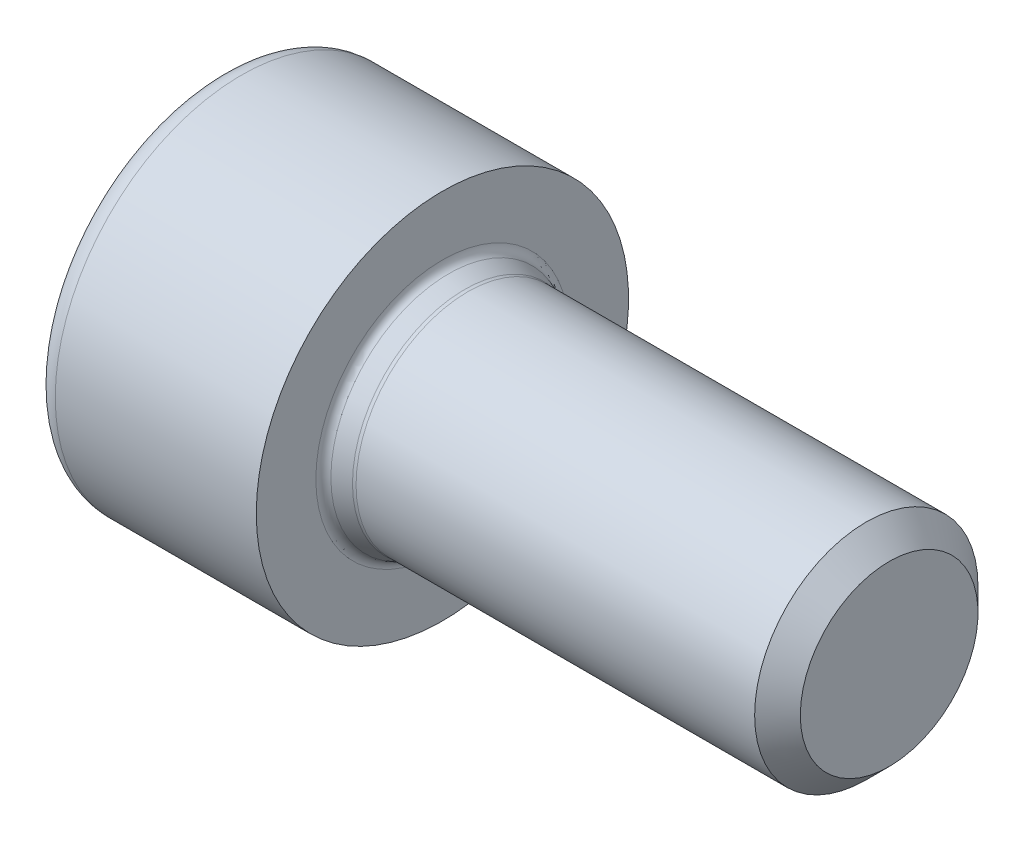
SolidWorks part; units mm, degrees
note: '?' marks a value the reader was unsure of.
ref_plane "前视基准面" through (0, 0, 0) normal (0, 0, 1) x (1, 0, 0)
ref_plane "上视基准面" through (0, 0, 0) normal (0, 1, 0) x (1, 0, 0)
ref_plane "右视基准面" through (0, 0, 0) normal (1, 0, 0) x (0, 0, -1)
sketch "草图1" plane through (0, 0, 0) normal (0, 0, 1) x (1, 0, 0)
  line L0 (-0.8566, 0) -> (-2.3, 2.5)
  line L1 (-2.3, 2.5) -> (-6, 2.5)
  line L2 (-6, 2.5) -> (-6, 4.4)
  line L3 (-5.4, 5) -> (0, 5)
  line L4 (0, 5) -> (0, 3.4)
  line L5 (0.1677, 3.1639) -> (0.5977, 3.0139)
  line L6 (0.68, 3) -> (11.3865, 3)
  line L7 (11.3865, 3) -> (12, 2.3865)
  line L8 (12, 2.3865) -> (12, 0)
  line L9 (12, 0) -> (-0.8566, 0)
  line L10 (12, 0) -> (-0.8566, 0) construction
  arc A0 (-6, 4.4) -> (-5.4, 5) centre (-5.4, 4.4) cw
  arc A1 (0, 3.4) -> (0.1677, 3.1639) centre (0.25, 3.4) ccw
  arc A2 (0.5977, 3.0139) -> (0.68, 3) centre (0.68, 3.25) ccw
revolve "旋转1" add sketch "草图1" angle 360 about L10
cosmetic thread "装饰螺纹线1" parameters "D1"=3, "D2"=4.773
ref_plane "基准面4" through (-2.3, 0, 0) normal (1, 0, 0) x (0, 0, -1)
sketch "草图2" plane through (-2.3, 0, 0) normal (1, 0, 0) x (0, 0, -1)
  line L0 (-2.5, 1.4434) -> (-2.5, -1.4434)
  line L1 (-2.5, -1.4434) -> (0, -2.8868)
  line L2 (0, -2.8868) -> (2.5, -1.4434)
  line L3 (2.5, -1.4434) -> (2.5, 1.4434)
  line L4 (2.5, 1.4434) -> (0, 2.8868)
  line L5 (0, 2.8868) -> (-2.5, 1.4434)
extrude "切除-拉伸1" cut sketch "草图2" against normal blind 6
ref_plane "基准面5" through (0, 0, 0) normal (1, 0, 0) x (0, 0, -1)
ref_plane "基准面6" through (12, 0, 0) normal (1, 0, 0) x (0, 0, -1)
ref_plane "基准面7" through (-6, 0, 0) normal (1, 0, 0) x (0, 0, -1)
ref_plane "IP1 XY" through (0, 0, 0) normal (1, 0, 0) x (0, 0, -1)
ref_plane "IP1 XZ" through (0, 0, 0) normal (0, -1, 0) x (-1, 0, 0)
ref_plane "IP1 YZ" through (0, 0, 0) normal (0, 0, -1) x (-1, 0, 0)
ref_axis "IP1 X" through (0, 0, 80.9) along (0, 0, -1)?
ref_axis "IP1 Y" through (0, -50, 0) along (0, 1, 0)?
ref_axis "IP1 Z" through (80.9, 0, 0) along (-1, 0, 0)?
sketch3d "IP1"
  point P0 (0, 0, 0)
ref_plane "IP3 XY" through (12, 0, 0) normal (1, 0, 0) x (0, 0, -1)
ref_plane "IP3 XZ" through (0, 0, 0) normal (0, -1, 0) x (-1, 0, 0)
ref_plane "IP3 YZ" through (0, 0, 0) normal (0, 0, -1) x (-1, 0, 0)
ref_axis "IP3 X" through (12, 0, 80.9) along (0, 0, -1)?
ref_axis "IP3 Y" through (12, -50, 0) along (0, 1, 0)?
ref_axis "IP3 Z" through (80.9, 0, 0) along (-1, 0, 0)?
sketch3d "IP3"
  point P0 (12, 0, 0)
ref_plane "IP2 XY" through (-6, 0, 0) normal (1, 0, 0) x (0, 0, -1)
ref_plane "IP2 XZ" through (0, 0, 0) normal (0, -1, 0) x (-1, 0, 0)
ref_plane "IP2 YZ" through (0, 0, 0) normal (0, 0, -1) x (-1, 0, 0)
ref_axis "IP2 X" through (-6, 0, 80.9) along (0, 0, -1)?
ref_axis "IP2 Y" through (-6, -50, 0) along (0, 1, 0)?
ref_axis "IP2 Z" through (80.9, 0, 0) along (-1, 0, 0)?
sketch3d "IP2"
  point P0 (-6, 0, 0)
ref_plane "IP4 XY" through (0, 0, 0) normal (1, 0, 0) x (0, 0, -1)
ref_plane "IP4 XZ" through (0, 0, 0) normal (0, -1, 0) x (-1, 0, 0)
ref_plane "IP4 YZ" through (0, 0, 0) normal (0, 0, -1) x (-1, 0, 0)
ref_axis "IP4 X" through (0, 0, 80.9) along (0, 0, -1)?
ref_axis "IP4 Y" through (0, -50, 0) along (0, 1, 0)?
ref_axis "IP4 Z" through (80.9, 0, 0) along (-1, 0, 0)?
sketch3d "IP4"
  point P0 (0, 0, 0)
sketch "草图3" plane through (0, 0, 0) normal (1, 0, 0) x (0, 0, -1)
  circle A0 centre (0, 0) radius 3.75
extrude "凸台-拉伸1" add sketch "草图3" against normal blind 3 separate body
other "删除面1" face at (-3, 0, -3.75)
